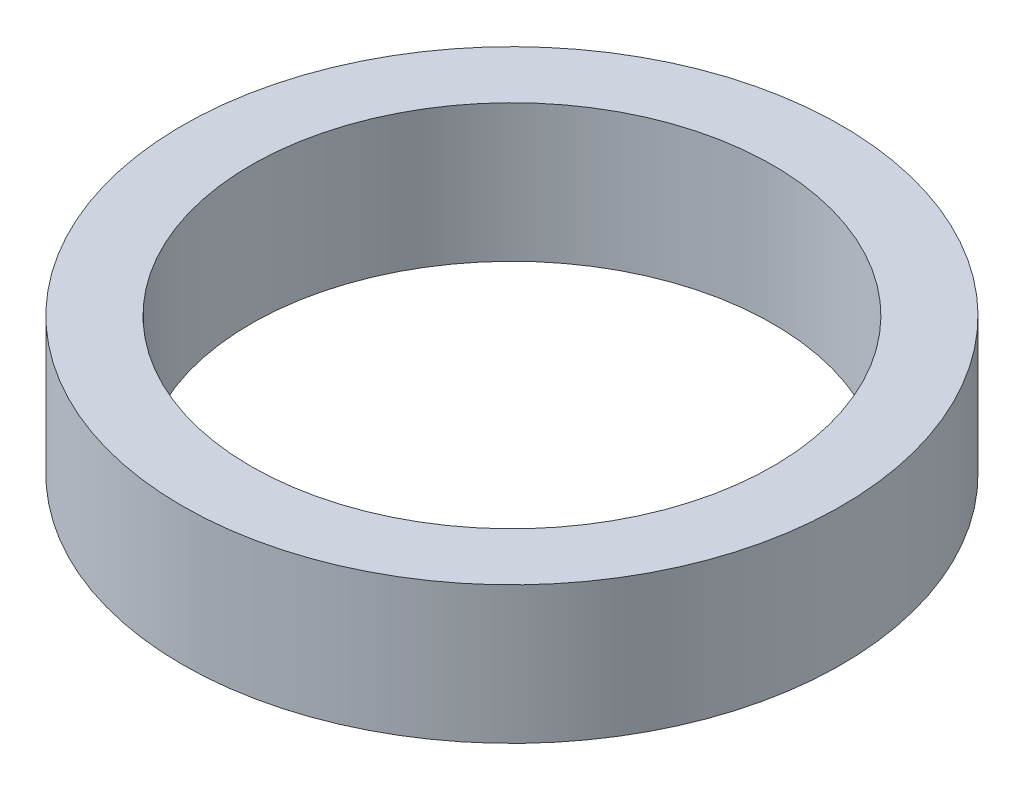
SolidWorks part; units mm, degrees
ref_plane "Front Plane" through (0, 0, 0) normal (0, 0, 1) x (1, 0, 0)
ref_plane "Top Plane" through (0, 0, 0) normal (0, 1, 0) x (1, 0, 0)
ref_plane "Right Plane" through (0, 0, 0) normal (1, 0, 0) x (0, 0, -1)
sketch "Sketch1" plane through (0, 0, 0) normal (0, 1, 0) x (1, 0, 0)
  circle A0 centre (0, 0) radius 60
  dimension "FLANGE_OD" = 120
extrude "Boss-Extrude1" add sketch "Sketch1" along normal blind 25
sketch "Sketch2" plane through (0, 0, 0) normal (0, 1, 0) x (1, 0, 0)
  circle A0 centre (0, 0) radius 47.5
  dimension "BORE_D" = 95
extrude "Cut-Extrude1" cut sketch "Sketch2" along normal through all
sketch "Sketch3" plane through (0, 25, 0) normal (0, 1, 0) x (1, 0, 0)
  circle A0 centre (0, 0) radius 27.0801 construction
  circle A1 centre (-27.0801, 0) radius 2.1703
  dimension "BOLT_D" = 4.3406
  dimension "BOLT_PCD" = 54.1601
extrude "Cut-Extrude2" cut sketch "Sketch3" against normal blind 23.88 rebuild error yes
pattern_circular "CirPattern1" count 3 over 360 rebuild error yes
